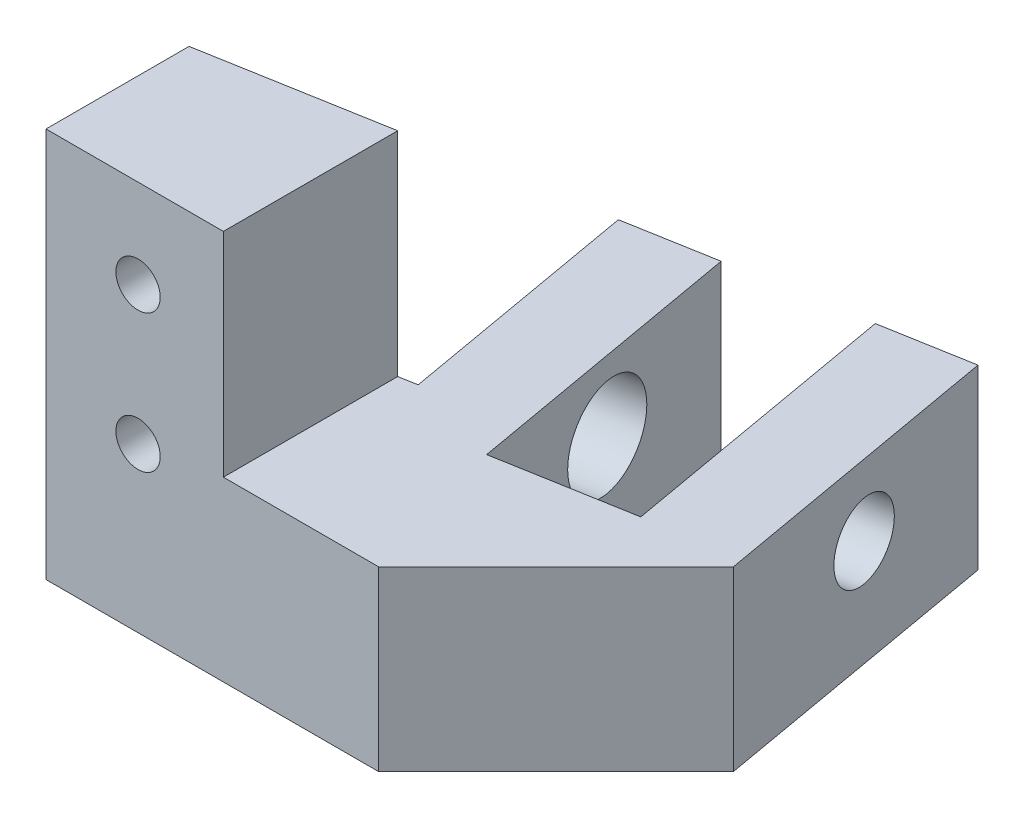
SolidWorks part; units mm, degrees
ref_plane "Plan de face" through (0, 0, 0) normal (0, 0, 1) x (1, 0, 0)
ref_plane "Plan de dessus" through (0, 0, 0) normal (0, 1, 0) x (1, 0, 0)
ref_plane "Plan de droite" through (0, 0, 0) normal (1, 0, 0) x (0, 0, -1)
sketch "Esquisse1" plane through (0, 0, 0) normal (0, 0, 1) x (1, 0, 0)
  line L0 (0, 0) -> (28.75, 0)
  line L1 (28.75, 0) -> (28.75, 10)
  line L2 (28.75, 10) -> (10, 10)
  line L3 (10, 10) -> (10, 22)
  line L4 (10, 22) -> (0, 22)
  line L5 (0, 22) -> (0, 0)
  dimension "D1" = 10
  dimension "D2" = 22
  dimension "D3" = 10
  dimension "D4" = 18.75
extrude "Boss.-Extru.1" add sketch "Esquisse1" along normal blind 10
sketch "Esquisse2" plane through (0, 10, 0) normal (0, 1, 0) x (1, 0, 0)
  line L0 (28.75, 0) -> (25.798, 16.7417)
  line L1 (25.798, 16.7417) -> (20.8739, 15.8735)
  line L2 (20.8739, 15.8735) -> (23.6729, 0)
  line L3 (28.75, 0) -> (10, 0) construction
  line L4 (23.6729, 0) -> (28.75, 0)
  line L5 (16.0572, 0) -> (13.4879, 14.5711)
  line L6 (13.4879, 14.5711) -> (8.5638, 13.7029)
  line L7 (8.5638, 13.7029) -> (10.98, 0)
  line L8 (16.0572, 0) -> (10.98, 0)
  line L9 (28.75, -10) -> (28.75, 0) construction
  dimension "D1" = 5
  dimension "D2" = 7.5
  dimension "D3" = 190
  dimension "D4" = 17
extrude "Boss.-Extru.2" add sketch "Esquisse2" against normal up to surface (10 mm away) up to face at (14.375, 0, 5)
sketch "Esquisse3" plane through (0, 10, 0) normal (0, 1, 0) x (1, 0, 0)
  line L0 (16.0572, 0) -> (16.3176, -1.4772)
  line L1 (16.3176, -1.4772) -> (23.7037, -0.1749)
  line L2 (23.7037, -0.1749) -> (23.6729, 0)
  line L3 (20.8739, 15.8735) -> (23.6729, 0) construction
  line L4 (16.0572, 0) -> (13.4879, 14.5711) construction
  line L5 (23.6729, 0) -> (16.0572, 0)
  dimension "D1" = 1.5
extrude "Enlèv. mat.-Extru.1" cut sketch "Esquisse3" against normal up to next
sketch "Esquisse4" plane through (10.6489, 0, -1.8777) normal (-0.9848, 0, 0.1736) x (0.1736, 0, 0.9848)
  line L0 (-12.0076, 10) -> (1.9067, 10) construction
  line L1 (1.9067, 0) -> (1.9067, 10) construction
  circle A0 centre (-4.0933, 6) radius 2.75
  dimension "D2" = 5.5
  dimension "D1" = 4
  dimension "D3" = 6
extrude "Enlèv. mat.-Extru.2" cut sketch "Esquisse4" against normal up to next
sketch "Esquisse5" plane through (22.959, 0, -4.0483) normal (-0.9848, 0, 0.1736) x (0.1736, 0, 0.9848)
  circle A0 centre (-4.0933, 6) radius 2.1
  circle A1 centre (-4.0933, 6) radius 2.75 construction
  circle A2 centre (-4.0933, 6) radius 2.75 construction
  dimension "D1" = 4.2
extrude "Enlèv. mat.-Extru.3" cut sketch "Esquisse5" against normal up to next
chamfer "Chanfrein1" distance 10 angle 45 1 edges at (28.75, 5, 10)
sketch "Esquisse6" plane through (0, 22, 0) normal (0, 1, 0) x (1, 0, 0)
  line L0 (0, 0) -> (10.98, 0)
  line L1 (10.98, 0) -> (0, -1.9361)
  line L2 (0, -10) -> (0, 0) construction
  line L3 (0, -1.9361) -> (0, 0)
  line L4 (8.5638, 13.7029) -> (10.98, 0) construction
extrude "Enlèv. mat.-Extru.4" cut sketch "Esquisse6" against normal up to next
sketch "Esquisse7" plane through (0, 0, 10) normal (0, 0, 1) x (1, 0, 0)
  line L0 (0, 22) -> (0, 0) construction
  line L1 (10, 22) -> (0, 22) construction
  circle A0 centre (5.19, 17) radius 1.25
  circle A1 centre (5.19, 9.22) radius 1.25
  dimension "D1" = 2.5
  dimension "D2" = 5.19
  dimension "D3" = 5
  dimension "D4" = 7.78
extrude "Enlèv. mat.-Extru.5" cut sketch "Esquisse7" against normal up to next
